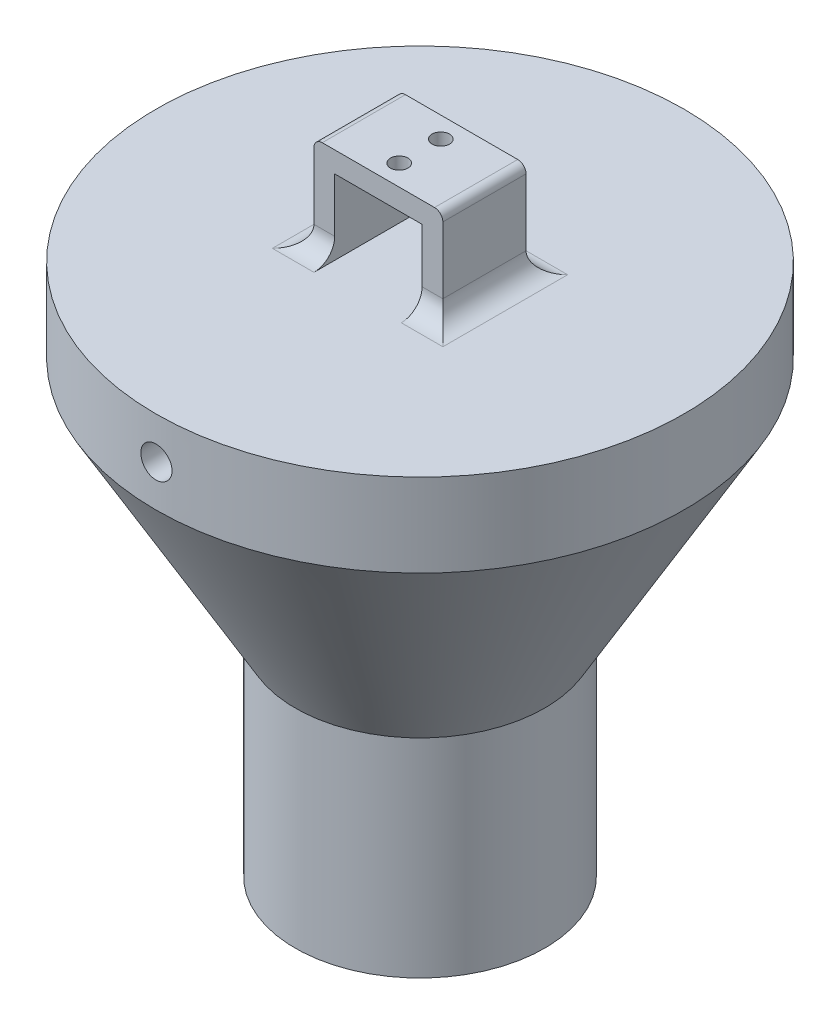
SolidWorks part; units mm, degrees
ref_plane "Front Plane" through (0, 0, 0) normal (0, 0, 1) x (1, 0, 0)
ref_plane "Top Plane" through (0, 0, 0) normal (0, 1, 0) x (1, 0, 0)
ref_plane "Right Plane" through (0, 0, 0) normal (1, 0, 0) x (0, 0, -1)
sketch "Sketch1" plane through (0, 0, 0) normal (0, 0, 1) x (1, 0, 0)
  line L0 (0, 0) -> (0, 88)
  line L1 (0, 0) -> (-30, 0)
  line L2 (-30, 0) -> (-30, 50)
  line L3 (-30, 50) -> (-63.4863, 108)
  line L5 (-63.4863, 108) -> (-63.4863, 128)
  line L6 (-63.4863, 128) -> (0, 128)
  line L7 (0, 128) -> (0, 88)
  line L8 (-30, 50) -> (0, 50)
  dimension "D1" = 88
  dimension "D2" = 30
  dimension "D3" = 50
  dimension "D4" = 150
  dimension "D5" = 20
  dimension "D6" = 63.4863
revolve "Revolve1" add sketch "Sketch1" angle 360 about L0 region at (-26.7225, 93.7976, 0)
shell "Shell1" thickness 10 removed face at (0, 50, -30)
sketch "Sketch4" plane through (0, 0, 0) normal (0, 0, 1) x (1, 0, 0)
  line L0 (0, 128) -> (0, 108) construction
  line L1 (63.4863, 128) -> (-63.4863, 128) construction
  line L2 (63.4863, 108) -> (-63.4863, 108) construction
  circle A0 centre (0, 118) radius 3.75
  dimension "D1" = 7.5
extrude "Cut-Extrude2" cut sketch "Sketch4" against normal mid plane 150
revolve "Revolve2" add sketch "Sketch1<3>" angle 360 about L0 region at (-15, 25, 0)
sketch "Sketch1<3>" plane through (0, 0, 0) normal (0, 0, 1) x (1, 0, 0) same geometry as "Sketch1"
shell "Shell3" thickness 12 removed face at (0, 0, -30) removed face at (0, 50, 18.453)
sketch "Sketch5" plane through (0, 0, 0) normal (0, -1, 0) x (1, 0, 0)
  circle A0 centre (0, 0) radius 20.5
  circle A1 centre (0, 0) radius 25.5
  dimension "D1" = 41
  dimension "D2" = 51
extrude "Cut-Extrude3" cut sketch "Sketch5" against normal blind 3.6
sketch "Sketch7" plane through (0, 0, 0) normal (0, 0, 1) x (1, 0, 0)
  line L0 (0, 128) -> (0, 143) construction
  line L1 (63.4863, 128) -> (-63.4863, 128) construction
  line L2 (7.5, 128) -> (10.5, 128)
  line L3 (-7.5, 128) -> (7.5, 128) construction
  line L4 (-7.5, 128) -> (-7.5, 143) construction
  line L5 (-7.5, 143) -> (7.5, 143) construction
  line L6 (7.5, 128) -> (7.5, 143) construction
  line L7 (-7.5, 128) -> (7.5, 143) construction
  line L8 (-7.5, 143) -> (7.5, 128) construction
  line L9 (10.5, 128) -> (10.5, 146)
  line L10 (10.5, 146) -> (-10.5, 146)
  line L11 (-10.5, 128) -> (-10.5, 146)
  line L12 (10.5, 128) -> (15.5, 128)
  line L13 (15.5, 128) -> (15.5, 151)
  line L14 (15.5, 151) -> (-15.5, 151)
  line L15 (-15.5, 128) -> (-15.5, 151)
  line L16 (-10.5, 128) -> (-15.5, 128)
  point P5 (0, 135.5)
  point P15 (0, 146)
  point P20 (0, 151)
  dimension "D1" = 15
  dimension "D2" = 15
  dimension "D3" = 3
  dimension "D4" = 3
  dimension "D5" = 5
  dimension "D6" = 5
extrude "Boss-Extrude1" add sketch "Sketch7" along normal mid plane 20 contours L16 L11 L10 L9 L12 L13 L14 L15 region at (10.886, 137, 0)
sketch "Sketch8" plane through (0, 151, 0) normal (0, 1, 0) x (1, 0, 0)
  line L0 (0, 10) -> (0, 0) construction
  line L1 (15.5, 10) -> (-15.5, 10) construction
  line L2 (0, 0) -> (0, -10) construction
  line L3 (-15.5, 0) -> (15.5, 0) construction
  line L4 (-15.5, -10) -> (-15.5, 10) construction
  line L5 (15.5, -10) -> (15.5, 10) construction
  line L6 (15.5, -10) -> (-15.5, -10) construction
  circle A0 centre (0, 5) radius 2.1
  circle A1 centre (0, -5) radius 2.1
  dimension "D1" = 4.2
extrude "Cut-Extrude4" cut sketch "Sketch8" against normal blind 10
fillet "Fillet1" radius 5 6 edges at (15.5, 128, 0) (-15.5, 128, 0) (13, 128, -10) (-13, 128, -10) (13, 128, 10) (-13, 128, 10)
fillet "Fillet2" radius 2 2 edges at (-15.5, 151, 0) (15.5, 151, 0)
sketch "Sketch9" plane through (0, 0, 0) normal (0, -1, 0) x (1, 0, 0)
  line L0 (0, 30) -> (0, 25.5) construction
  circle A0 centre (0, 0) radius 30 construction
  circle A1 centre (0, 0) radius 25.5 construction
  circle A2 centre (0, 27.75) radius 1
  circle A3 centre (19.6222, 19.6222) radius 1
  circle A4 centre (27.75, 0) radius 1
  circle A5 centre (19.6222, -19.6222) radius 1
  circle A6 centre (0, -27.75) radius 1
  circle A7 centre (-19.6222, -19.6222) radius 1
  circle A8 centre (-27.75, 0) radius 1
  circle A9 centre (-19.6222, 19.6222) radius 1
  point P26 (0, 0)
  dimension "D1" = 2
  dimension "D2" = 8
extrude "Cut-Extrude5" cut sketch "Sketch9" against normal blind 0.3
